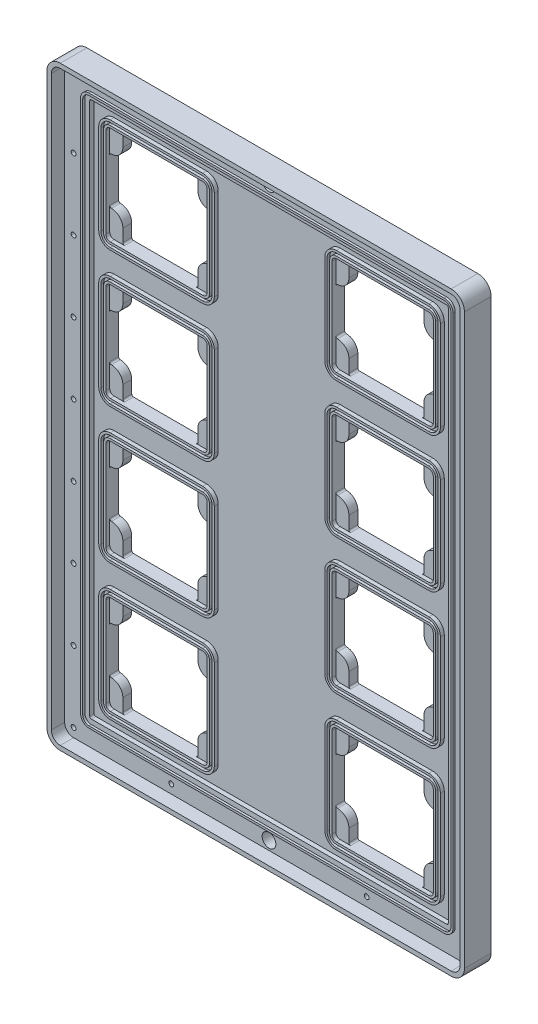
SolidWorks part; units mm, degrees
ref_plane "Front Plane" through (0, 0, 0) normal (0, 0, 1) x (1, 0, 0)
ref_plane "Top Plane" through (0, 0, 0) normal (0, 1, 0) x (1, 0, 0)
ref_plane "Right Plane" through (0, 0, 0) normal (1, 0, 0) x (0, 0, -1)
sketch "Sketch1" plane through (0, 0, 0) normal (0, 0, 1) x (1, 0, 0)
  line L1 (0, 0) -> (292.1, 0)
  line L2 (0, 0) -> (0, 419.1)
  line L3 (0, 419.1) -> (292.1, 419.1)
  line L4 (292.1, 0) -> (292.1, 419.1)
  dimension "D1" = 419.1
  dimension "D2" = 292.1
extrude "Boss-Extrude1" add sketch "Sketch1" along normal blind 9.525
sketch "Sketch4" plane through (0, 0, 9.525) normal (0, 0, 1) x (1, 0, 0)
  line L3 (0, 419.1) -> (0, 0) construction
  line L4 (6.35, 412.75) -> (285.75, 412.75) construction
  line L5 (6.35, 412.75) -> (6.35, 6.35) construction
  line L6 (6.35, 6.35) -> (285.75, 6.35) construction
  line L7 (285.75, 412.75) -> (285.75, 6.35) construction
  line L8 (292.1, 419.1) -> (0, 419.1) construction
  line L9 (292.1, 0) -> (292.1, 419.1) construction
  line L10 (0, 0) -> (292.1, 0) construction
  circle A0 centre (6.35, 6.35) radius 1.7272
  circle A1 centre (6.35, 412.75) radius 1.7272
  circle A2 centre (285.75, 412.75) radius 1.7272
  circle A3 centre (285.75, 6.35) radius 1.7272
  dimension "D5" = 3.4544
  dimension "D1" = 6.35
  dimension "D2" = 6.35
  dimension "D3" = 6.35
  dimension "D4" = 6.35
extrude "Cut-Extrude1" cut sketch "Sketch4" against normal blind 6.985
pattern_linear "LPattern2" count 8 spacing 50.8 along (0, -1, 0) of "Cut-Extrude1"
pattern_linear "LPattern3" count 4 spacing 69.85 along (-1, 0, 0) of "Cut-Extrude1"
sketch "Sketch5" plane through (0, 0, 9.525) normal (0, 0, 1) x (1, 0, 0)
  line L0 (0, 419.1) -> (0, 0) construction
  line L1 (19.05, 406.4) -> (273.05, 406.4) construction
  line L2 (12.7, 400.05) -> (12.7, 19.05) construction
  line L3 (19.05, 12.7) -> (273.05, 12.7) construction
  line L4 (279.4, 400.05) -> (279.4, 19.05) construction
  line L5 (292.1, 419.1) -> (0, 419.1) construction
  line L6 (292.1, 0) -> (292.1, 419.1) construction
  line L7 (0, 0) -> (292.1, 0) construction
  line L8 (19.05, 14.732) -> (273.05, 14.732) construction
  line L9 (14.732, 400.05) -> (14.732, 19.05) construction
  line L10 (19.05, 404.368) -> (273.05, 404.368) construction
  line L11 (277.368, 400.05) -> (277.368, 19.05) construction
  line L12 (12.954, 400.05) -> (12.954, 19.05)
  line L13 (19.05, 406.146) -> (273.05, 406.146)
  line L14 (279.146, 400.05) -> (279.146, 19.05)
  line L15 (19.05, 12.954) -> (273.05, 12.954)
  line L16 (277.622, 400.05) -> (277.622, 19.05)
  line L17 (19.05, 404.622) -> (273.05, 404.622)
  line L18 (14.478, 400.05) -> (14.478, 19.05)
  line L19 (19.05, 14.478) -> (273.05, 14.478)
  arc A0 (273.05, 12.7) -> (279.4, 19.05) centre (273.05, 19.05) ccw construction
  arc A1 (12.7, 19.05) -> (19.05, 12.7) centre (19.05, 19.05) ccw construction
  arc A2 (273.05, 406.4) -> (279.4, 400.05) centre (273.05, 400.05) cw construction
  arc A3 (19.05, 406.4) -> (12.7, 400.05) centre (19.05, 400.05) ccw construction
  arc A4 (14.732, 19.05) -> (19.05, 14.732) centre (19.05, 19.05) ccw construction
  arc A5 (19.05, 404.368) -> (14.732, 400.05) centre (19.05, 400.05) ccw construction
  arc A6 (273.05, 404.368) -> (277.368, 400.05) centre (273.05, 400.05) cw construction
  arc A7 (273.05, 14.732) -> (277.368, 19.05) centre (273.05, 19.05) ccw construction
  arc A8 (19.05, 406.146) -> (12.954, 400.05) centre (19.05, 400.05) ccw
  arc A9 (273.05, 406.146) -> (279.146, 400.05) centre (273.05, 400.05) cw
  arc A10 (273.05, 12.954) -> (279.146, 19.05) centre (273.05, 19.05) ccw
  arc A11 (12.954, 19.05) -> (19.05, 12.954) centre (19.05, 19.05) ccw
  arc A12 (273.05, 404.622) -> (277.622, 400.05) centre (273.05, 400.05) cw
  arc A13 (19.05, 404.622) -> (14.478, 400.05) centre (19.05, 400.05) ccw
  arc A14 (14.478, 19.05) -> (19.05, 14.478) centre (19.05, 19.05) ccw
  arc A15 (273.05, 14.478) -> (277.622, 19.05) centre (273.05, 19.05) ccw
  dimension "D5" = 6.35
  dimension "D1" = 12.7
  dimension "D2" = 12.7
  dimension "D3" = 12.7
  dimension "D4" = 12.7
  dimension "D6" = 2.032
  dimension "D7" = 2.032
  dimension "D8" = 0.254
  dimension "D9" = 0.254
  dimension "D10" = 0.254
sketch "Sketch6" plane through (0, 0, 9.525) normal (0, 0, 1) x (1, 0, 0)
  line L24 (273.05, 401.193) -> (19.05, 401.193)
  line L25 (274.193, 19.05) -> (274.193, 400.05)
  line L26 (19.05, 17.907) -> (273.05, 17.907)
  line L27 (17.907, 400.05) -> (17.907, 19.05)
  line L28 (273.05, 401.193) -> (19.05, 401.193)
  line L29 (274.193, 19.05) -> (274.193, 400.05)
  line L30 (19.05, 17.907) -> (273.05, 17.907)
  line L31 (17.907, 400.05) -> (17.907, 19.05)
  arc A20 (19.05, 401.193) -> (17.907, 400.05) centre (19.05, 400.05) ccw
  arc A21 (274.193, 400.05) -> (273.05, 401.193) centre (273.05, 400.05) ccw
  arc A22 (273.05, 17.907) -> (274.193, 19.05) centre (273.05, 19.05) ccw
  arc A23 (17.907, 19.05) -> (19.05, 17.907) centre (19.05, 19.05) ccw
  arc A24 (19.05, 401.193) -> (17.907, 400.05) centre (19.05, 400.05) ccw
  arc A25 (274.193, 400.05) -> (273.05, 401.193) centre (273.05, 400.05) ccw
  arc A26 (273.05, 17.907) -> (274.193, 19.05) centre (273.05, 19.05) ccw
  arc A27 (17.907, 19.05) -> (19.05, 17.907) centre (19.05, 19.05) ccw
  dimension "D1" = 3.175
extrude "Cut-Extrude3" cut sketch "Sketch6" against normal blind 3.175
extrude "Boss-Extrude2" add sketch "Sketch5" along normal blind 1.5875 contours L12 A11 L15 A10 L14 A9 L13 A8 A15 L19 A14 L18 A13 L17 A12 L16 region at (15.0752, 404.0248, 9.525)
sketch "Sketch7" plane through (0, 0, 9.525) normal (0, 0, 1) x (1, 0, 0)
  circle A0 centre (146.05, 6.35) radius 4.9022
  circle A1 centre (146.05, 412.75) radius 4.9022
  dimension "D1" = 9.8044
extrude "Cut-Extrude4" cut sketch "Sketch7" against normal through all
fillet "Fillet1" radius 6.35 4 edges at (0, 419.1, 4.7625) (292.1, 419.1, 4.7625) (0, 0, 4.7625) (292.1, 0, 4.7625)
sketch "Sketch8" plane through (0, 0, 0) normal (0, 0, -1) x (-1, 0, 0)
  line L0 (-264.668, 370.459) -> (-264.668, 339.2678)
  line L1 (-255.27, 329.8698) -> (-255.27, 320.8782)
  line L2 (-252.4506, 318.0588) -> (-201.2442, 318.0588)
  line L3 (-198.4248, 320.8782) -> (-198.4248, 329.8698)
  line L4 (-189.0268, 339.2678) -> (-189.0268, 370.459)
  line L5 (-198.4248, 379.857) -> (-198.4248, 388.8486)
  line L6 (-201.2442, 391.668) -> (-252.4506, 391.668)
  line L7 (-255.27, 388.8486) -> (-255.27, 379.857)
  line L8 (-261.8486, 391.668) -> (-261.8486, 318.0588) construction
  line L9 (-264.668, 388.8486) -> (-189.0268, 388.8486) construction
  line L10 (-264.668, 391.668) -> (-189.0268, 391.668) construction
  line L11 (-264.668, 391.668) -> (-264.668, 318.0588) construction
  line L12 (-264.668, 318.0588) -> (-189.0268, 318.0588) construction
  line L13 (-189.0268, 391.668) -> (-189.0268, 318.0588) construction
  line L14 (-264.668, 379.857) -> (-189.0268, 379.857) construction
  line L15 (-264.668, 370.459) -> (-189.0268, 370.459) construction
  line L16 (-264.668, 339.2678) -> (-189.0268, 339.2678) construction
  line L17 (-264.668, 329.8698) -> (-189.0268, 329.8698) construction
  line L18 (-264.668, 320.8782) -> (-189.0268, 320.8782) construction
  line L19 (-255.27, 318.0588) -> (-255.27, 391.668) construction
  line L20 (-252.4506, 391.668) -> (-252.4506, 318.0588) construction
  line L21 (-201.2442, 391.668) -> (-201.2442, 318.0588) construction
  line L22 (-198.4248, 391.668) -> (-198.4248, 318.0588) construction
  line L23 (-191.8462, 318.0588) -> (-191.8462, 391.668) construction
  line L24 (-189.0268, 373.2784) -> (-264.668, 373.2784) construction
  line L27 (-201.2442, 393.7) -> (-252.4506, 393.7)
  line L28 (-257.302, 388.8486) -> (-257.302, 379.857)
  line L29 (-266.7, 370.459) -> (-266.7, 339.2678)
  line L30 (-257.302, 329.8698) -> (-257.302, 320.8782)
  line L31 (-252.4506, 316.0268) -> (-201.2442, 316.0268)
  line L32 (-196.3928, 320.8782) -> (-196.3928, 329.8698)
  line L33 (-186.9948, 339.2678) -> (-186.9948, 370.459)
  line L34 (-196.3928, 379.857) -> (-196.3928, 388.8486)
  line L35 (-285.75, 419.1) -> (-6.35, 419.1) construction
  line L36 (-292.1, 6.35) -> (-292.1, 412.75) construction
  arc A0 (-261.8486, 373.2784) -> (-255.27, 379.857) centre (-261.8486, 379.857) ccw
  arc A1 (-261.8486, 373.2784) -> (-264.668, 370.459) centre (-261.8486, 370.459) ccw
  arc A2 (-264.668, 339.2678) -> (-261.8486, 336.4484) centre (-261.8486, 339.2678) ccw
  arc A3 (-255.27, 329.8698) -> (-261.8486, 336.4484) centre (-261.8486, 329.8698) ccw
  arc A4 (-255.27, 320.8782) -> (-252.4506, 318.0588) centre (-252.4506, 320.8782) ccw
  arc A5 (-201.2442, 318.0588) -> (-198.4248, 320.8782) centre (-201.2442, 320.8782) ccw
  arc A6 (-191.8462, 336.4484) -> (-198.4248, 329.8698) centre (-191.8462, 329.8698) ccw
  arc A7 (-191.8462, 336.4484) -> (-189.0268, 339.2678) centre (-191.8462, 339.2678) ccw
  arc A8 (-189.0268, 370.459) -> (-191.8462, 373.2784) centre (-191.8462, 370.459) ccw
  arc A9 (-198.4248, 379.857) -> (-191.8462, 373.2784) centre (-191.8462, 379.857) ccw
  arc A10 (-198.4248, 388.8486) -> (-201.2442, 391.668) centre (-201.2442, 388.8486) ccw
  arc A11 (-252.4506, 391.668) -> (-255.27, 388.8486) centre (-252.4506, 388.8486) ccw
  arc A12 (-252.4506, 393.7) -> (-257.302, 388.8486) centre (-252.4506, 388.8486) ccw
  arc A13 (-261.8486, 375.3104) -> (-257.302, 379.857) centre (-261.8486, 379.857) ccw
  arc A14 (-261.8486, 375.3104) -> (-266.7, 370.459) centre (-261.8486, 370.459) ccw
  arc A15 (-266.7, 339.2678) -> (-261.8486, 334.4164) centre (-261.8486, 339.2678) ccw
  arc A16 (-257.302, 329.8698) -> (-261.8486, 334.4164) centre (-261.8486, 329.8698) ccw
  arc A17 (-257.302, 320.8782) -> (-252.4506, 316.0268) centre (-252.4506, 320.8782) ccw
  arc A18 (-201.2442, 316.0268) -> (-196.3928, 320.8782) centre (-201.2442, 320.8782) ccw
  arc A19 (-191.8462, 334.4164) -> (-196.3928, 329.8698) centre (-191.8462, 329.8698) ccw
  arc A20 (-191.8462, 334.4164) -> (-186.9948, 339.2678) centre (-191.8462, 339.2678) ccw
  arc A21 (-186.9948, 370.459) -> (-191.8462, 375.3104) centre (-191.8462, 370.459) ccw
  arc A22 (-196.3928, 379.857) -> (-191.8462, 375.3104) centre (-191.8462, 379.857) ccw
  arc A23 (-196.3928, 388.8486) -> (-201.2442, 393.7) centre (-201.2442, 388.8486) ccw
  dimension "D4" = 11.811
  dimension "D5" = 21.209
  dimension "D6" = 52.4002
  dimension "D1" = 73.6092
  dimension "D2" = 75.6412
  dimension "D3" = 2.8194
  dimension "D7" = 61.7982
  dimension "D8" = 70.7898
  dimension "D9" = 2.8194
  dimension "D10" = 9.398
  dimension "D11" = 12.2174
  dimension "D12" = 63.4238
  dimension "D13" = 66.2432
  dimension "D14" = 72.8218
  dimension "D15" = 55.2196
  dimension "D16" = 25.4
  dimension "D17" = 25.4
  dimension "D18" = 2.032
extrude "Cut-Extrude5" cut sketch "Sketch8" against normal blind 3.175
sketch "Sketch10" plane through (0, 0, 0) normal (0, 0, -1) x (-1, 0, 0)
  line L18 (-263.0805, 370.459) -> (-263.0805, 339.2678)
  line L19 (-253.6825, 329.8698) -> (-253.6825, 320.8782)
  line L20 (-252.4506, 319.6463) -> (-201.2442, 319.6463)
  line L21 (-200.0123, 320.8782) -> (-200.0123, 329.8698)
  line L22 (-190.6143, 339.2678) -> (-190.6143, 370.459)
  line L23 (-200.0123, 379.857) -> (-200.0123, 388.8486)
  line L24 (-201.2442, 390.0805) -> (-252.4506, 390.0805)
  line L25 (-253.6825, 388.8486) -> (-253.6825, 379.857)
  line L26 (-263.0805, 370.459) -> (-263.0805, 339.2678)
  line L27 (-253.6825, 329.8698) -> (-253.6825, 320.8782)
  line L28 (-252.4506, 319.6463) -> (-201.2442, 319.6463)
  line L29 (-200.0123, 320.8782) -> (-200.0123, 329.8698)
  line L30 (-190.6143, 339.2678) -> (-190.6143, 370.459)
  line L31 (-200.0123, 379.857) -> (-200.0123, 388.8486)
  line L32 (-201.2442, 390.0805) -> (-252.4506, 390.0805)
  line L33 (-253.6825, 388.8486) -> (-253.6825, 379.857)
  arc A28 (-261.8486, 371.6909) -> (-263.0805, 370.459) centre (-261.8486, 370.459) ccw
  arc A29 (-263.0805, 339.2678) -> (-261.8486, 338.0359) centre (-261.8486, 339.2678) ccw
  arc A30 (-253.6825, 329.8698) -> (-261.8486, 338.0359) centre (-261.8486, 329.8698) ccw
  arc A31 (-253.6825, 320.8782) -> (-252.4506, 319.6463) centre (-252.4506, 320.8782) ccw
  arc A32 (-201.2442, 319.6463) -> (-200.0123, 320.8782) centre (-201.2442, 320.8782) ccw
  arc A33 (-191.8462, 338.0359) -> (-200.0123, 329.8698) centre (-191.8462, 329.8698) ccw
  arc A34 (-191.8462, 338.0359) -> (-190.6143, 339.2678) centre (-191.8462, 339.2678) ccw
  arc A35 (-190.6143, 370.459) -> (-191.8462, 371.6909) centre (-191.8462, 370.459) ccw
  arc A36 (-200.0123, 379.857) -> (-191.8462, 371.6909) centre (-191.8462, 379.857) ccw
  arc A37 (-200.0123, 388.8486) -> (-201.2442, 390.0805) centre (-201.2442, 388.8486) ccw
  arc A38 (-252.4506, 390.0805) -> (-253.6825, 388.8486) centre (-252.4506, 388.8486) ccw
  arc A39 (-261.8486, 371.6909) -> (-253.6825, 379.857) centre (-261.8486, 379.857) ccw
  arc A40 (-261.8486, 371.6909) -> (-263.0805, 370.459) centre (-261.8486, 370.459) ccw
  arc A41 (-263.0805, 339.2678) -> (-261.8486, 338.0359) centre (-261.8486, 339.2678) ccw
  arc A42 (-253.6825, 329.8698) -> (-261.8486, 338.0359) centre (-261.8486, 329.8698) ccw
  arc A43 (-253.6825, 320.8782) -> (-252.4506, 319.6463) centre (-252.4506, 320.8782) ccw
  arc A44 (-201.2442, 319.6463) -> (-200.0123, 320.8782) centre (-201.2442, 320.8782) ccw
  arc A45 (-191.8462, 338.0359) -> (-200.0123, 329.8698) centre (-191.8462, 329.8698) ccw
  arc A46 (-191.8462, 338.0359) -> (-190.6143, 339.2678) centre (-191.8462, 339.2678) ccw
  arc A47 (-190.6143, 370.459) -> (-191.8462, 371.6909) centre (-191.8462, 370.459) ccw
  arc A48 (-200.0123, 379.857) -> (-191.8462, 371.6909) centre (-191.8462, 379.857) ccw
  arc A49 (-200.0123, 388.8486) -> (-201.2442, 390.0805) centre (-201.2442, 388.8486) ccw
  arc A50 (-252.4506, 390.0805) -> (-253.6825, 388.8486) centre (-252.4506, 388.8486) ccw
  arc A51 (-261.8486, 371.6909) -> (-253.6825, 379.857) centre (-261.8486, 379.857) ccw
  dimension "D1" = 1.5875
extrude "Cut-Extrude6" cut sketch "Sketch10" against normal through all
sketch "Sketch11" plane through (0, 0, 0) normal (0, 0, -1) x (-1, 0, 0)
  line L0 (-226.8474, 388.8994) -> (-226.8474, 393.7) construction
  line L1 (-261.8486, 388.8994) -> (-191.8462, 388.8994) construction
  line L2 (-261.8486, 388.8994) -> (-261.8486, 320.8274) construction
  line L3 (-261.8486, 320.8274) -> (-191.8462, 320.8274) construction
  line L4 (-191.8462, 388.8994) -> (-191.8462, 320.8274) construction
  line L5 (-201.2442, 393.7) -> (-252.4506, 393.7) construction
  line L6 (-226.8474, 320.8274) -> (-226.8474, 316.0268) construction
  line L7 (-252.4506, 316.0268) -> (-201.2442, 316.0268) construction
  line L8 (-261.8486, 354.8634) -> (-266.7, 354.8634) construction
  line L9 (-266.7, 370.459) -> (-266.7, 339.2678) construction
  line L10 (-191.8462, 354.8634) -> (-186.9948, 354.8634) construction
  line L11 (-186.9948, 339.2678) -> (-186.9948, 370.459) construction
  circle A0 centre (-261.8486, 388.8994) radius 1.1303
  circle A1 centre (-191.8462, 388.8994) radius 1.1303
  circle A2 centre (-191.8462, 320.8274) radius 1.1303
  circle A3 centre (-261.8486, 320.8274) radius 1.1303
  dimension "D3" = 2.2606
  dimension "D1" = 70.0024
  dimension "D2" = 68.072
extrude "Cut-Extrude7" cut sketch "Sketch11" against normal blind 3.9688
sketch "Sketch12" plane through (0, 0, 6.35) normal (0, 0, 1) x (1, 0, 0)
  line L0 (252.4506, 390.0805) -> (201.2442, 390.0805) construction
  line L1 (193.7893, 390.0805) -> (259.9055, 390.0805)
  line L2 (190.6143, 386.9055) -> (190.6143, 322.8213)
  line L3 (193.7893, 319.6463) -> (259.9055, 319.6463)
  line L4 (263.0805, 386.9055) -> (263.0805, 322.8213)
  line L5 (263.0805, 339.2678) -> (263.0805, 370.459) construction
  line L10 (193.7893, 391.668) -> (259.9055, 391.668)
  line L11 (264.668, 386.9055) -> (264.668, 322.8213)
  line L12 (193.7893, 318.0588) -> (259.9055, 318.0588)
  line L13 (189.0268, 386.9055) -> (189.0268, 322.8213)
  line L14 (187.1218, 386.9055) -> (187.1218, 322.8213)
  line L15 (193.7893, 316.1538) -> (259.9055, 316.1538)
  line L16 (266.573, 386.9055) -> (266.573, 322.8213)
  line L17 (193.7893, 393.573) -> (259.9055, 393.573)
  line L18 (185.5343, 386.9055) -> (185.5343, 322.8213)
  line L19 (193.7893, 314.5663) -> (259.9055, 314.5663)
  line L20 (268.1605, 386.9055) -> (268.1605, 322.8213)
  line L21 (193.7893, 395.1605) -> (259.9055, 395.1605)
  line L22 (201.2442, 319.6463) -> (252.4506, 319.6463) construction
  line L23 (190.6143, 370.459) -> (190.6143, 339.2678) construction
  arc A0 (259.9055, 319.6463) -> (263.0805, 322.8213) centre (259.9055, 322.8213) ccw
  arc A1 (190.6143, 322.8213) -> (193.7893, 319.6463) centre (193.7893, 322.8213) ccw
  arc A2 (259.9055, 390.0805) -> (263.0805, 386.9055) centre (259.9055, 386.9055) cw
  arc A3 (193.7893, 390.0805) -> (190.6143, 386.9055) centre (193.7893, 386.9055) ccw
  arc A4 (259.9055, 391.668) -> (264.668, 386.9055) centre (259.9055, 386.9055) cw
  arc A5 (259.9055, 318.0588) -> (264.668, 322.8213) centre (259.9055, 322.8213) ccw
  arc A6 (189.0268, 322.8213) -> (193.7893, 318.0588) centre (193.7893, 322.8213) ccw
  arc A7 (193.7893, 391.668) -> (189.0268, 386.9055) centre (193.7893, 386.9055) ccw
  arc A8 (187.1218, 322.8213) -> (193.7893, 316.1538) centre (193.7893, 322.8213) ccw
  arc A9 (259.9055, 316.1538) -> (266.573, 322.8213) centre (259.9055, 322.8213) ccw
  arc A10 (259.9055, 393.573) -> (266.573, 386.9055) centre (259.9055, 386.9055) cw
  arc A11 (193.7893, 393.573) -> (187.1218, 386.9055) centre (193.7893, 386.9055) ccw
  arc A12 (185.5343, 322.8213) -> (193.7893, 314.5663) centre (193.7893, 322.8213) ccw
  arc A13 (259.9055, 314.5663) -> (268.1605, 322.8213) centre (259.9055, 322.8213) ccw
  arc A14 (259.9055, 395.1605) -> (268.1605, 386.9055) centre (259.9055, 386.9055) cw
  arc A15 (193.7893, 395.1605) -> (185.5343, 386.9055) centre (193.7893, 386.9055) ccw
  dimension "D1" = 3.175
  dimension "D2" = 1.5875
  dimension "D3" = 1.905
  dimension "D4" = 1.5875
extrude "Boss-Extrude3" add sketch "Sketch12" along normal blind 2.794 contours L21 A15 L18 A12 L19 A13 L20 A14 A11 L17 A10 L16 A9 L15 A8 L14 | L10 A7 L13 A6 L12 A5 L11 A4 A3 L1 A2 L4 A0 L3 A1 L2 region at (226.8474, 390.6125, 6.35) region at (188.7683, 391.9265, 6.35)
extrude "Boss-Extrude4" add sketch "Sketch12<3>" along normal blind 0.7937 contours L17 A11 L14 A8 L15 A9 L16 A10 A7 L10 A4 L11 A5 L12 A6 L13 region at (189.8591, 390.8357, 6.35)
sketch "Sketch12<3>" plane through (0, 0, 6.35) normal (0, 0, 1) x (1, 0, 0) same geometry as "Sketch12"
pattern_linear "LPattern1" count 2 spacing 161.5948 along (-1, 0, 0) count 4 spacing 96.8756 along (0, -1, 0) of "Cut-Extrude6", "Cut-Extrude5", "Cut-Extrude7", "Boss-Extrude3", "Boss-Extrude4"
sketch "Sketch13" plane through (0, 0, 0) normal (0, 0, -1) x (-1, 0, 0)
  line L4 (-6.35, 419.1) -> (-285.75, 419.1)
  line L5 (-292.1, 412.75) -> (-292.1, 6.35)
  line L6 (-285.75, 0) -> (-6.35, 0)
  line L7 (0, 6.35) -> (0, 412.75)
  line L8 (-285.75, -3.175) -> (-6.35, -3.175)
  line L9 (3.175, 6.35) -> (3.175, 412.75)
  line L10 (-6.35, 422.275) -> (-285.75, 422.275)
  line L11 (-295.275, 412.75) -> (-295.275, 6.35)
  line L12 (-285.75, -3.175) -> (-6.35, -3.175)
  line L13 (3.175, 6.35) -> (3.175, 412.75)
  line L14 (-6.35, 422.275) -> (-285.75, 422.275)
  line L15 (-295.275, 412.75) -> (-295.275, 6.35)
  arc A4 (-285.75, 419.1) -> (-292.1, 412.75) centre (-285.75, 412.75) ccw
  arc A5 (-292.1, 6.35) -> (-285.75, 0) centre (-285.75, 6.35) ccw
  arc A6 (-6.35, 0) -> (0, 6.35) centre (-6.35, 6.35) ccw
  arc A7 (0, 412.75) -> (-6.35, 419.1) centre (-6.35, 412.75) ccw
  arc A8 (-295.275, 6.35) -> (-285.75, -3.175) centre (-285.75, 6.35) ccw
  arc A9 (-6.35, -3.175) -> (3.175, 6.35) centre (-6.35, 6.35) ccw
  arc A10 (3.175, 412.75) -> (-6.35, 422.275) centre (-6.35, 412.75) ccw
  arc A11 (-285.75, 422.275) -> (-295.275, 412.75) centre (-285.75, 412.75) ccw
  arc A12 (-295.275, 6.35) -> (-285.75, -3.175) centre (-285.75, 6.35) ccw
  arc A13 (-6.35, -3.175) -> (3.175, 6.35) centre (-6.35, 6.35) ccw
  arc A14 (3.175, 412.75) -> (-6.35, 422.275) centre (-6.35, 412.75) ccw
  arc A15 (-285.75, 422.275) -> (-295.275, 412.75) centre (-285.75, 412.75) ccw
  dimension "D1" = 3.175
  dimension "D2" = 3.175
extrude "Boss-Extrude5" add sketch "Sketch13" against normal blind 19.05
